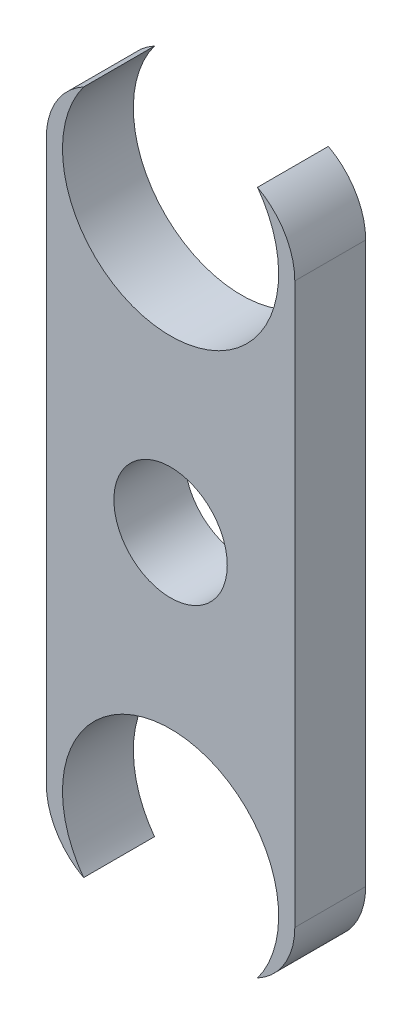
SolidWorks part; units mm, degrees
ref_plane "Front Plane" through (0, 0, 0) normal (1, 0, 0) x (0, 1, 0)
ref_plane "Top Plane" through (0, 0, 0) normal (0, 0, 1) x (0, 1, 0)
ref_plane "Right Plane" through (0, 0, 0) normal (0, 1, 0) x (-1, 0, 0)
sketch "Sketch1" plane through (0, 0, 0) normal (0, 0, 1) x (0, 1, 0)
  line L0 (-48.3122, 12.2653) -> (-48.3122, 17.5302)
  line L1 (-48.3122, -17.5302) -> (48.3122, -17.5302)
  line L2 (-48.3122, -17.5302) -> (-48.3122, -12.2653)
  line L3 (-48.3122, 17.5302) -> (48.3122, 17.5302)
  line L4 (48.3122, -17.5302) -> (48.3122, -12.2653)
  line L5 (-48.3122, -17.5302) -> (48.3122, 17.5302) construction
  line L6 (-48.3122, 17.5302) -> (48.3122, -17.5302) construction
  line L7 (-24, 0) -> (-8, 0) construction
  line L8 (0, 17.5302) -> (0, -17.5302) construction
  line L9 (24, 0) -> (8, 0) construction
  line L10 (48.3122, -17.5302) -> (48.3122, -12.2653)
  line L11 (48.3122, 12.2653) -> (48.3122, 17.5302)
  line L12 (48.3122, 12.2653) -> (48.3122, 17.5302)
  circle A0 centre (0, 0) radius 8
  arc A1 (-48.3122, -12.2653) -> (-48.3122, 12.2653) centre (-39.25, 0) ccw
  arc A2 (48.3122, -12.2653) -> (48.3122, 12.2653) centre (39.25, 0) cw
  point P0 (0, 0)
  dimension "D1" = 16
  dimension "D2" = 30.5
extrude "Boss-Extrude1" add sketch "Sketch1" along normal blind 10 contours L4 A2 L11 L3 L0 A1 L2 L1 A0 region at (-14.8978, -47.2844, 0)
fillet "Fillet1" radius 10 4 edges at (-17.5302, 48.3122, 5) (-17.5302, -48.3122, 5) (17.5302, -48.3122, 5) (17.5302, 48.3122, 5)
sketch "78.5" plane through (0, 0, 10) normal (0, 0, 1) x (1, 0, 0)
  line L0 (0, 39.25) -> (0, -39.25) construction
  point P4 (0, 0)
